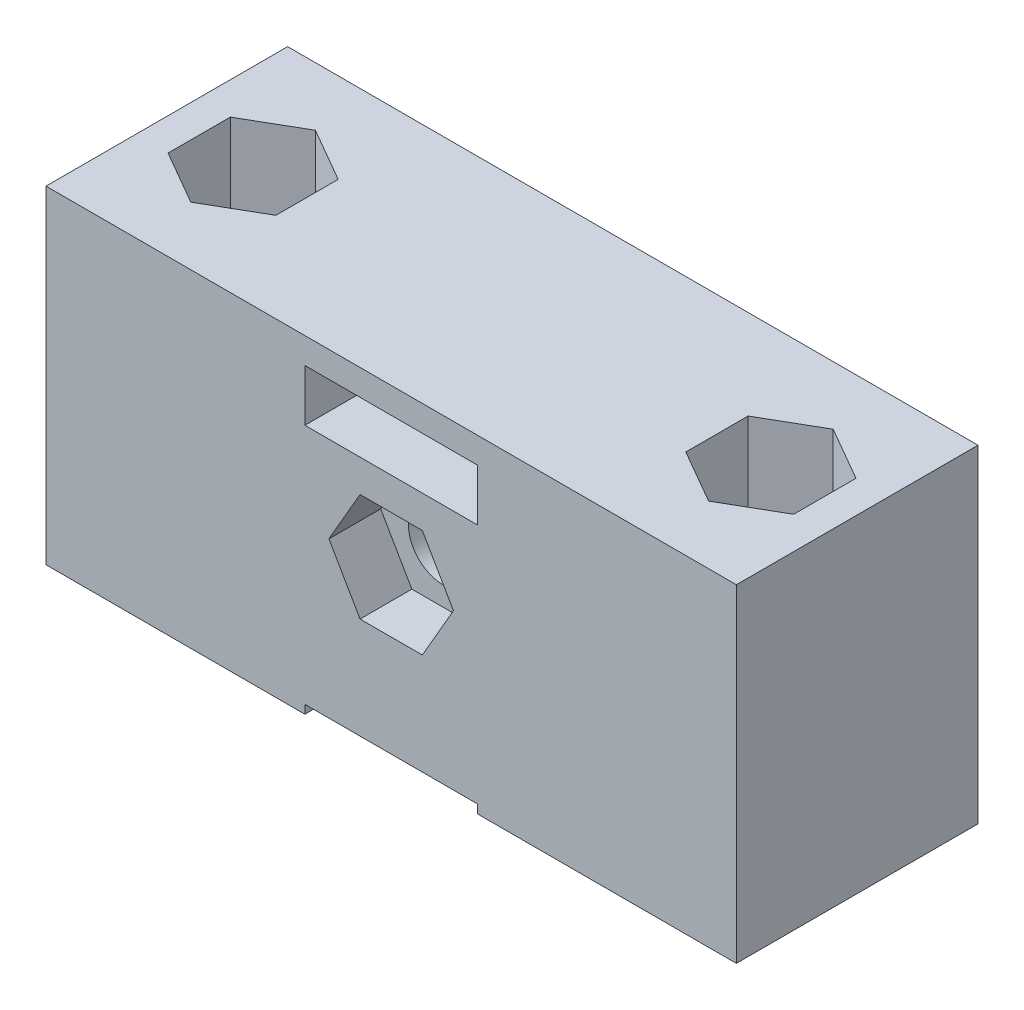
SolidWorks part; units mm, degrees
ref_plane "Front Plane" through (0, 0, 0) normal (0, 0, 1) x (1, 0, 0)
ref_plane "Top Plane" through (0, 0, 0) normal (0, 1, 0) x (1, 0, 0)
ref_plane "Right Plane" through (0, 0, 0) normal (1, 0, 0) x (0, 0, -1)
sketch "Sketch1" plane through (0, 0, 0) normal (0, 1, 0) x (1, 0, 0)
  line L1 (-20, 7) -> (20, 7)
  line L2 (-20, 7) -> (-20, -7)
  line L3 (-20, -7) -> (20, -7)
  line L4 (20, 7) -> (20, -7)
  line L5 (-20, 7) -> (20, -7) construction
  line L6 (-20, -7) -> (20, 7) construction
  point P0 (0, 0)
  dimension "D1" = 40
  dimension "D2" = 14
extrude "Boss-Extrude1" add sketch "Sketch1" along normal blind 19
sketch "Sketch2" plane through (0, 0, 7) normal (0, 0, 1) x (1, 0, 0)
  line L0 (0, 19) -> (0, 0) construction
  line L1 (-20, 19) -> (20, 19) construction
  line L3 (-5, 14.5) -> (5, 14.5)
  line L4 (-5, 14.5) -> (-5, 17.5)
  line L5 (-5, 17.5) -> (5, 17.5)
  line L6 (5, 14.5) -> (5, 17.5)
  line L7 (-5, 14.5) -> (5, 17.5) construction
  line L8 (-5, 17.5) -> (5, 14.5) construction
  line L9 (-5, -0.5) -> (5, -0.5)
  line L10 (-5, -0.5) -> (-5, 0.5)
  line L11 (-5, 0.5) -> (5, 0.5)
  line L12 (5, -0.5) -> (5, 0.5)
  line L13 (-5, -0.5) -> (5, 0.5) construction
  line L14 (-5, 0.5) -> (5, -0.5) construction
  point P5 (0, 16)
  dimension "D1" = 10
  dimension "D2" = 3
  dimension "D3" = 16
  dimension "D4" = 10
  dimension "D5" = 1
extrude "Cut-Extrude1" cut sketch "Sketch2" against normal blind 30
sketch "Sketch3" plane through (0, 0, 7) normal (0, 0, 1) x (1, 0, 0)
  line L0 (0, 19) -> (0, 0) construction
  line L1 (-20, 19) -> (20, 19) construction
  circle A0 centre (0, 9.5) radius 2
  dimension "D1" = 4
extrude "Cut-Extrude2" cut sketch "Sketch3" against normal through all
sketch "Sketch4" plane through (0, 19, 0) normal (0, 1, 0) x (1, 0, 0)
  line L0 (-20, 0) -> (20, 0) construction
  line L1 (-20, 7) -> (-20, -7) construction
  line L2 (20, -7) -> (20, 7) construction
  line L3 (0, 7) -> (0, -7) construction
  line L4 (20, 7) -> (-20, 7) construction
  line L5 (-20, -7) -> (20, -7) construction
  circle A0 centre (-15, 0) radius 1.6
  circle A1 centre (15, 0) radius 1.6
  dimension "D1" = 3.2
  dimension "D2" = 15
extrude "Cut-Extrude3" cut sketch "Sketch4" against normal through all
sketch "Sketch8" plane through (0, 0, 0) normal (0, -1, 0) x (-1, 0, 0)
  line L0 (-5, 7) -> (-5, -7) construction
  line L1 (5, -7) -> (-5, -7)
  line L2 (5, -7) -> (5, -6)
  line L3 (5, -6) -> (-5, -6)
  line L4 (-5, -7) -> (-5, -6)
  dimension "D1" = 1
extrude "Boss-Extrude2" [suppressed] add sketch "Sketch8" against normal up to next
sketch "Sketch9" plane through (0, 19, 0) normal (0, 1, 0) x (1, 0, 0)
  line L0 (0, 7) -> (0, -7) construction
  line L1 (-15, 3.6084) -> (-18.125, 1.8042)
  line L2 (-18.125, 1.8042) -> (-18.125, -1.8042)
  line L3 (-18.125, -1.8042) -> (-15, -3.6084)
  line L4 (-15, -3.6084) -> (-11.875, -1.8042)
  line L5 (-11.875, -1.8042) -> (-11.875, 1.8042)
  line L6 (-11.875, 1.8042) -> (-15, 3.6084)
  line L7 (20, 7) -> (-20, 7) construction
  line L8 (-20, -7) -> (20, -7) construction
  line L9 (11.875, 1.8042) -> (15, 3.6084)
  line L10 (11.875, -1.8042) -> (11.875, 1.8042)
  line L11 (15, -3.6084) -> (11.875, -1.8042)
  line L12 (18.125, -1.8042) -> (15, -3.6084)
  line L13 (18.125, 1.8042) -> (18.125, -1.8042)
  line L14 (15, 3.6084) -> (18.125, 1.8042)
  circle A0 centre (-15, 0) radius 3.125 construction
  circle A1 centre (15, 0) radius 3.125 construction
  dimension "D1" = 6.25
extrude "Cut-Extrude4" cut sketch "Sketch9" against normal blind 10
sketch "Sketch10" plane through (0, 0, 7) normal (0, 0, 1) x (1, 0, 0)
  line L1 (1.8042, 12.625) -> (-1.8042, 12.625)
  line L2 (-1.8042, 12.625) -> (-3.6084, 9.5)
  line L3 (-3.6084, 9.5) -> (-1.8042, 6.375)
  line L4 (-1.8042, 6.375) -> (1.8042, 6.375)
  line L5 (1.8042, 6.375) -> (3.6084, 9.5)
  line L6 (3.6084, 9.5) -> (1.8042, 12.625)
  circle A0 centre (0, 9.5) radius 3.125 construction
  dimension "D1" = 6.25
extrude "Cut-Extrude5" cut sketch "Sketch10" against normal blind 3
equation "\"X-ROD-SPACING\"=45"
equation "\"Y-ROD-SPACING\"=75"
equation "\"Z-ROD-SPACING\"=17.5"
equation "\"Y-BED-OFFSET\"=2"
equation "\"Y-BED-ROD-INSET\"=3.5"
equation "\"Y-BED-SCREW-SPACING\"=209"
equation "\"Y-BED-SCREW-CUTOUT-SLOT-HEIGHT\"=2"
equation "\"T-SLOT-NUT-FILLET-RADIUS\"=0.5"
equation "\"T-SLOT-SCREW-SHAFT-RADIUS\"=1.55"
equation "\"T-SLOT-SCREW-SHAFT-CUTOUT-LENGTH\"=11"
equation "\"T-SLOT-NUT-DEPTH\"=3.5"
equation "\"T-SLOT-NUT-WIDTH\"=2.85"
equation "\"T-SLOT-NUT-END-DISTANCE\"=8"
equation "\"ACRYLIC-THICKNESS\"=10"
equation "\"ACRYLIC-THICKNESS2\"=4.5"
equation "\"ACRYLIC-TAB-CUTOUT-SIZE\"=\"ACRYLIC-THICKNESS\"+\"ACRYLIC-TAB-TOLERANCE\"*2"
equation "\"ACRYLIC-TAB-TOLERANCE\"=-.05"
equation "\"ACRYLIC-TAB-WIDTH\"=\"ACRYLIC-THICKNESS\""
equation "\"ACRYLIC-M3-HOLE\"=2.9"
equation "\"SMOOTHROD-CAP-SCREW-DISTANCE\"=20"
equation "\"FRAME-WIDTH-INNER\"=370"
equation "\"NEMA17-HOLE-SPACING\"=31"
equation "\"NEMA17-CENTRAL-CUTOUT\"=22.5"
equation "\"Z-BRACKET-REACH\"=55"
equation "\"Z-ROD-INSET\"=13.5"
equation "\"TOP-BRACKET-SPACING\"=40"
equation "\"SMOOTHROD-X-LENGTH\"=350"
equation "\"SMOOTHROD-Y-LENGTH\"=350"
equation "\"SMOOTHROD-Z-LENGTH\"=350"
equation "\"SMOOTHROD-TIGHTENING-HEADROOM\"=.25"
equation "\"LEADSCREW-Z-LENGTH\"=300"
equation "\"SCREW-LENGTH-FRAME\"=\"ACRYLIC-THICKNESS\" + 10"
equation "\"SCREW-LENGTH-MOTOR\"=\"ACRYLIC-THICKNESS\" + 5"
equation "\"SCREW-LENGTH-EXTRUDER\"=28"
equation "\"SCREW-HEAD-RADIUS\"=6"
equation "\"PRINTED-M3-HOLE\"=3.5"
equation "\"PRINTED-X-SMOOTHROD-DIAMETER\"=9.0"
equation "\"PRINTED-X-SMOOTHROD-CUTOUT\"=10"
equation "\"PRINTED-X-BASE-HEIGHT\"=10"
equation "\"PRINTED-LM8UU-CUTOUT-SIZE\"=15.5"
equation "\"PRINTED-LM8UU-CUTOUT-LENGTH\"=24.5"
equation "\"PRINTED-X-IDLER-HEIGHT\"=16"
equation "\"PSU-MOUNTING-WIDTH\"=95"
equation "\"PSU-MOUNTING-HEIGHT\"=177"
equation "\"Y-BELT-TO-ROD-DISTANCE\"=20"
equation "\"SPOOL-HOLDER-ROD-SPACING\"=150"
equation "\"ACRYLIC-X-CARRIAGE-WIDTH\"=55"
equation "\"ACRYLIC-X-CARRIAGE-HEIGHT\"=75"
equation "\"ACRYLIC-X-CARRIAGE-LM8UU-CUTOUT-WIDTH\"=24.25"
equation "\"ACRYLIC-X-CARRIAGE-LM8UU-CUTOUT-HEIGHT\"=11.0"
equation "\"ACRYLIC-X-CARRIAGE-SCREW-SPACING-X\"=15"
equation "\"ACRYLIC-X-CARRIAGE-SCREW-SPACING-Y\"=33"
equation "\"ACRYLIC-X-CARRIAGE-CENTER-TAB-SPACING\"=14"
equation "\"ACRYLIC-X-CARRIAGE-EXTRUDER-OFFSET\"=26"
equation "\"ACRYLIC-X-CARRIAGE-EXTRUDER-ANGLE\"=90"
equation "\"ACRYLIC-X-CARRIAGE-EXTRUDER-SHELF-DEPTH\"=\"ACRYLIC-X-CARRIAGE-EXTRUDER-OFFSET\" + 28"
equation "\"ACRYLIC-X-CARRIAGE-EXTRUDER-BRACE-SPACING\"=23"
equation "\"ACRYLIC-X-CARRIAGE-EXTRUDER-BRACE-TAB-OFFSET\"=20"
equation "\"ACRYLIC-X-CARRIAGE-EXTRUDER-BRACE-HEIGHT\"=35"
equation "\"ACRYLIC-X-CARRIAGE-EXTRUDER-BRACE-SCREW-SPACING\"=22"
equation "\"ACRYLIC-X-CARRIAGE-DUAL-WIDTH-MULTIPLIER\"=1.65"
equation "\"ACRYLIC-X-CARRIAGE-DUAL-HOTEND-SPACING\"=42"
equation "\"ACRYLIC-X-CARRIAGE-DUAL-WIDTH\"=75"
equation "\"ACRYLIC-X-CARRIAGE-DUAL-HOTEND-SEPARATION\"=36"
equation "\"ACRYLIC-X-CARRIAGE-DUAL-MOUNT-PLATE-DEPTH\"=75"
equation "\"ACRYLIC-X-CARRIAGE-DUAL-MOUNT-BRACE-WIDTH\"=33"
equation "\"ACRYLIC-X-CARRIAGE-DUAL-MOUNT-SCREW-WIDTH\"=40"
equation "\"BLOWER-FAN-WIDTH\"=15"
equation "\"PRINTED-M3-NUT-AF\"=6.25"
equation "\"D1@Sketch9\"=\"PRINTED-M3-NUT-AF\""
equation "\"D1@Sketch10\"=\"PRINTED-M3-NUT-AF\""
